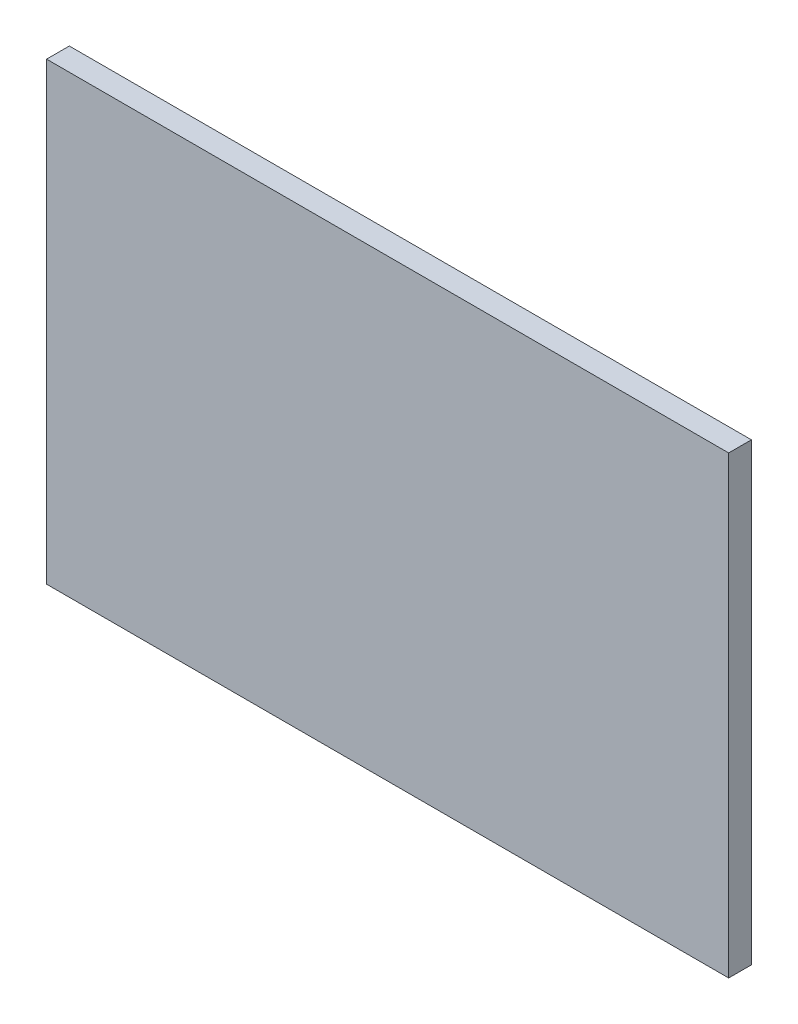
SolidWorks part; units mm, degrees
ref_plane "Alzado" through (0, 0, 0) normal (0, 0, 1) x (1, 0, 0)
ref_plane "Planta" through (0, 0, 0) normal (0, 1, 0) x (1, 0, 0)
ref_plane "Vista lateral" through (0, 0, 0) normal (1, 0, 0) x (0, 0, -1)
sketch "Croquis1" plane through (0, 0, 0) normal (0, 0, 1) x (1, 0, 0)
  line L1 (-294.9346, 8.7369) -> (5.0654, 8.7369)
  line L2 (-294.9346, 8.7369) -> (-294.9346, -191.2631)
  line L3 (-294.9346, -191.2631) -> (5.0654, -191.2631)
  line L4 (5.0654, 8.7369) -> (5.0654, -191.2631)
  line L5 (-294.9346, 8.7369) -> (5.0654, -191.2631) construction
  line L6 (-294.9346, -191.2631) -> (5.0654, 8.7369) construction
  point P0 (-144.9346, -91.2631)
  dimension "D1" = 300
  dimension "D2" = 200
extrude "Saliente-Extruir1" add sketch "Croquis1" along normal blind 10
sketch "Croquis3" plane through (0, 0, 10) normal (0, 0, 1) x (1, 0, 0)
  line L0 (-144.9346, 8.7369) -> (-144.9346, -191.2631) construction
  line L1 (5.0654, 8.7369) -> (-294.9346, 8.7369) construction
  line L2 (-294.9346, -191.2631) -> (5.0654, -191.2631) construction
  line L3 (-64.9346, 8.7369) -> (-224.9346, 8.7369)
  line L4 (-224.9346, 8.7369) -> (-224.9346, -191.2631)
  line L5 (-224.9346, -191.2631) -> (-147.357, -191.2631)
  line L7 (-64.9346, -191.2631) -> (-142.5121, -191.2631)
  line L8 (-64.9346, 8.7369) -> (-64.9346, -191.2631)
  dimension "D1" = 80
